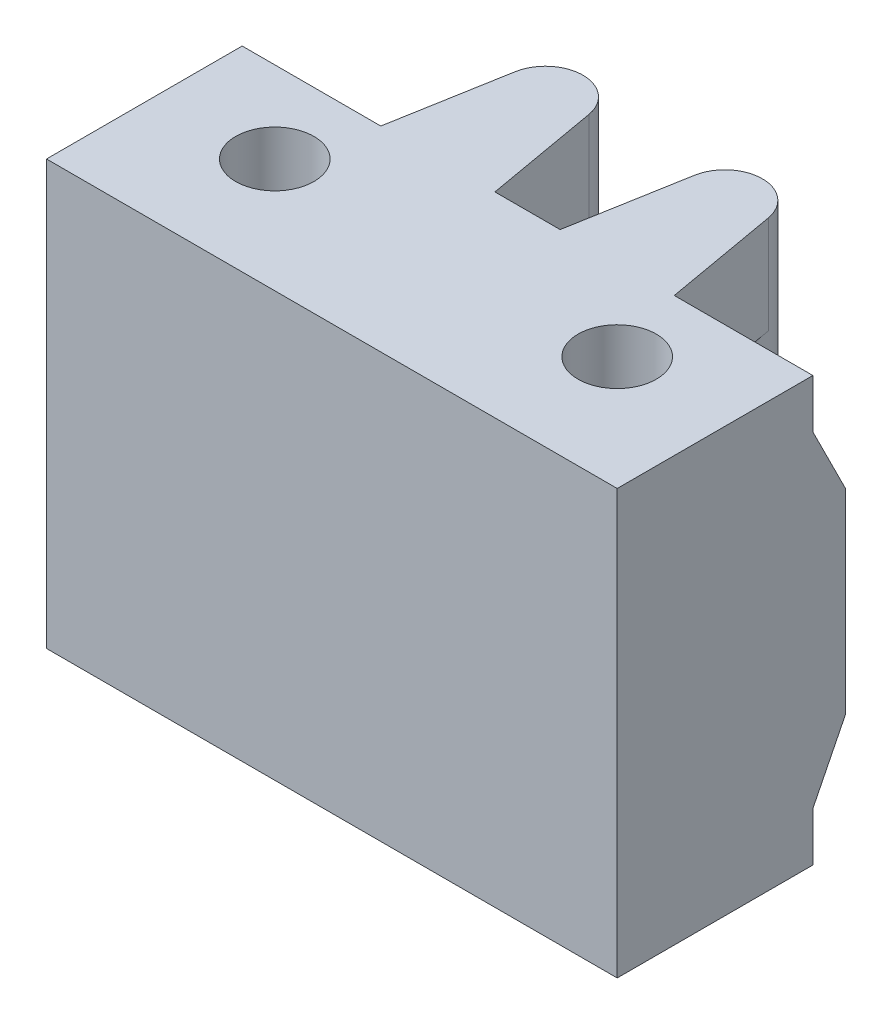
SolidWorks part; units mm, degrees
ref_plane "前基準面" through (0, 0, 0) normal (0, 0, 1) x (1, 0, 0)
ref_plane "上基準面" through (0, 0, 0) normal (0, 1, 0) x (1, 0, 0)
ref_plane "右基準面" through (0, 0, 0) normal (1, 0, 0) x (0, 0, -1)
ref_axis "基準軸1" through (0, -55, 0) along (0, 1, 0)
ref_axis "基準軸2" through (-88.99, 0, 0) along (1, 0, 0)
ref_axis "基準軸3" through (0, 0, 55) along (0, 0, -1)
sketch "草圖1" plane through (0, 0, 0) normal (0, 0, 1) x (1, 0, 0)
  line L1 (-17.5, 13) -> (0, 13)
  line L2 (-17.5, 13) -> (-17.5, 0)
  line L3 (-17.5, 0) -> (0, 0)
  line L4 (0, 13) -> (0, 0)
  point P7 (0, 0)
  point P8 (0, 0.9901)
  point P10 (-7.3658, 1.136)
  point P11 (-0.1647, 1.7031)
  point P12 (0, 1.8653)
  point P13 (0, 0)
  point P14 (0, 1.4277)
  point P15 (0, 1.2402)
  point P16 (-2.6352, 7.7629)
  dimension "D2" = 17.5
  dimension "D3" = 13
extrude "填料-伸長1" add sketch "草圖1" along normal blind 6
ref_plane "平面1" through (-8.75, 0, 0) normal (1, 0, 0) x (0, 0, -1)
sketch "草圖2" plane through (0, 13, 0) normal (0, 1, 0) x (1, 0, 0)
  line L0 (-12.6329, 3.5) -> (-13.25, 0)
  line L1 (-55, 0) -> (55, 0) construction
  line L2 (-10.3671, 3.5) -> (-9.75, 0)
  line L3 (-17.5, -6) -> (-17.5, 0) construction
  line L4 (-13.25, 0) -> (-9.75, 0)
  line L5 (-8.75, -3.3) -> (-8.75, 3.3) construction
  line L7 (-4.8671, 3.5) -> (-4.25, 0)
  line L8 (-7.1329, 3.5) -> (-7.75, 0)
  line L9 (-4.25, 0) -> (-7.75, 0)
  arc A0 (-10.3671, 3.5) -> (-12.6329, 3.5) centre (-11.5, 3.3002) ccw
  arc A1 (-7.1329, 3.5) -> (-4.8671, 3.5) centre (-6, 3.3002) cw
  dimension "D3" = 3.3002
  dimension "D7" = 80
  dimension "D8" = 80
  dimension "D9" = 4.25
  dimension "D10" = 3.5
extrude "填料-伸長2" add sketch "草圖2" against normal blind 3
ref_plane "平面2" through (0, 6.5, 0) normal (0, 1, 0) x (1, 0, 0)
mirror "鏡射1" about plane through (0, 6.5, 0) normal (0, 1, 0) of "填料-伸長2"
sketch "草圖3" plane through (0, 3, 0) normal (0, 1, 0) x (1, 0, 0)
  circle A0 centre (-11.5, 3.3002) radius 1.1503
  circle A1 centre (-6, 3.3002) radius 1.1503
  dimension "D1" = 2.3007
  dimension "D2" = 2.3007
extrude "填料-伸長3" add sketch "草圖3" along normal up to next
sketch "草圖4" plane through (-17.5, 0, 0) normal (-1, 0, 0) x (0, 0, 1)
  line L0 (0, 11.5) -> (0, 1.5)
  line L1 (0, -55) -> (0, 55) construction
  line L2 (0, 1.5) -> (-1, 3.5)
  line L3 (-1, 3.5) -> (-1, 9.5)
  line L4 (-1, 9.5) -> (0, 11.5)
  line L5 (5.1978, 6.5) -> (-5.1978, 6.5) construction
  point P5 (0, 6.5)
  point P10 (-1, 6.5)
  dimension "D1" = 10
  dimension "D2" = 6
  dimension "D3" = 1
extrude "填料-伸長4" add sketch "草圖4" against normal blind 3
mirror "鏡射2" about plane through (-8.75, 0, 0) normal (1, 0, 0) of "填料-伸長4"
sketch "草圖6" plane through (0, 13, 0) normal (0, 1, 0) x (1, 0, 0)
  line L0 (-55, 0) -> (55, 0) construction
  line L1 (-17.5, -6) -> (-17.5, 0) construction
  line L2 (0, -55) -> (0, 55) construction
  circle A0 centre (-14, -2.5) radius 1.2
  circle A1 centre (-3.5, -2.5) radius 1.2
  point P8 (-15.6566, -4.1038)
  dimension "D1" = 2.4
  dimension "D2" = 2.4
  dimension "D3" = 2.5
  dimension "D4" = 3.5
  dimension "D5" = 2.5
  dimension "D6" = 3.5
extrude "除料-伸長1" cut sketch "草圖6" against normal blind 5
mirror "鏡射3" about plane through (0, 6.5, 0) normal (0, 1, 0) of "除料-伸長1"
